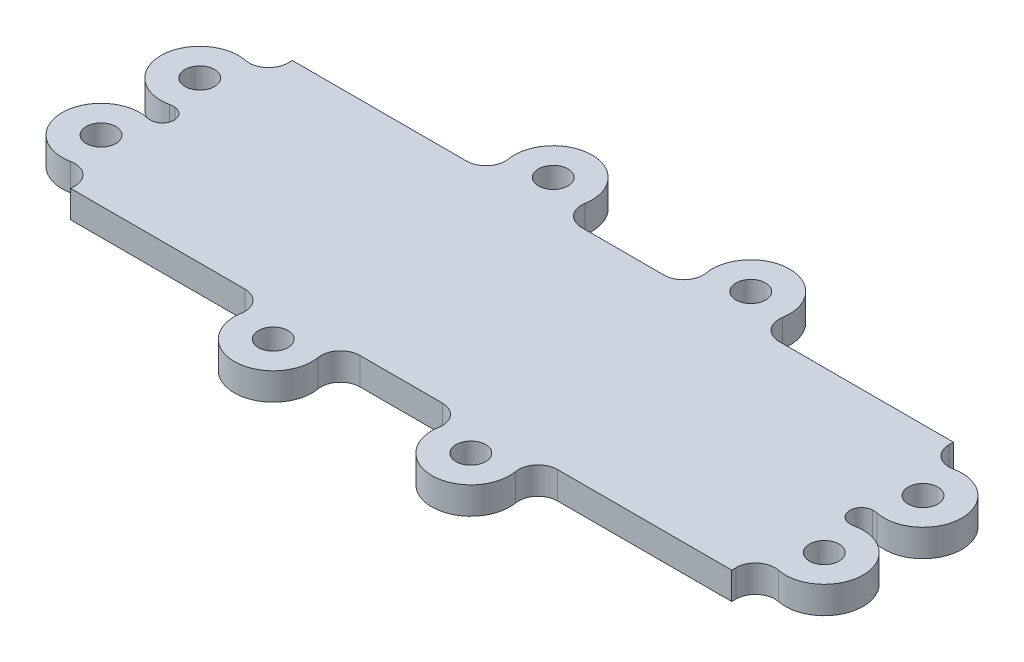
SolidWorks part; units mm, degrees
ref_plane "Front Plane" through (0, 0, 0) normal (0, 0, 1) x (1, 0, 0)
ref_plane "Top Plane" through (0, 0, 0) normal (0, 1, 0) x (1, 0, 0)
ref_plane "Right Plane" through (0, 0, 0) normal (1, 0, 0) x (0, 0, -1)
sketch "Sketch1" plane through (0, 0, 0) normal (0, 1, 0) x (1, 0, 0)
  line L1 (-85, 28.5) -> (85, 28.5)
  line L2 (-85, 28.5) -> (-85, -28.5)
  line L3 (-85, -28.5) -> (85, -28.5)
  line L4 (85, 28.5) -> (85, -28.5)
  line L5 (-85, 28.5) -> (85, -28.5) construction
  line L6 (-85, -28.5) -> (85, 28.5) construction
  point P0 (0, 0)
  dimension "D1" = 170
  dimension "D2" = 57
extrude "Boss-Extrude1" add sketch "Sketch1" along normal blind 7
sketch "Sketch2" plane through (0, 7, 0) normal (0, 1, 0) x (1, 0, 0)
  line L0 (-93, 12.7) -> (-93, -12.7) construction
  line L1 (-93, 0) -> (0, 0) construction
  line L2 (0, 0) -> (0, 36) construction
  line L3 (-25.4, 36) -> (25.4, 36) construction
  circle A0 centre (-25.4, 36) radius 10
  circle A1 centre (25.4, 36) radius 10
  circle A2 centre (-93, 12.7) radius 10
  circle A3 centre (-93, -12.7) radius 10
  circle A4 centre (-93, 12.7) radius 3.81
  circle A5 centre (-93, -12.7) radius 3.81
  circle A6 centre (-25.4, 36) radius 3.81
  circle A7 centre (25.4, 36) radius 3.81
  circle A8 centre (93, -12.7) radius 10
  circle A9 centre (93, -12.7) radius 3.81
  circle A10 centre (93, 12.7) radius 3.81
  circle A11 centre (93, 12.7) radius 10
  circle A12 centre (25.4, -36) radius 3.81
  circle A13 centre (-25.4, -36) radius 3.81
  circle A14 centre (25.4, -36) radius 10
  circle A15 centre (-25.4, -36) radius 10
  point P22 (0, 31.4857)
  point P23 (0, 36.7274)
  dimension "D2" = 20
  dimension "D3" = 7.62
  dimension "D1" = 25.4
  dimension "D4" = 93
  dimension "D5" = 50.8
  dimension "D6" = 36
extrude "Boss-Extrude2" add sketch "Sketch2" against normal up to surface (7 mm away) up to face at (0, 0, 0)
fillet "Fillet1" radius 5 16 edges at (-85, 3.5, 18.7) (-85, 3.5, 6.7) (-85, 3.5, -18.7) (18.7856, 3.5, -28.5) (-32.0144, 3.5, -28.5) (-18.7856, 3.5, -28.5) (32.0144, 3.5, -28.5) (85, 3.5, -18.7) (85, 3.5, 6.7) (85, 3.5, -6.7) (85, 3.5, 18.7) (32.0144, 3.5, 28.5) (-18.7856, 3.5, 28.5) (-85, 3.5, -6.7) (18.7856, 3.5, 28.5) (-32.0144, 3.5, 28.5)
fillet "Fillet2" radius 3 2 edges at (85.4161, 3.5, 0) (-85.4161, 3.5, 0)
